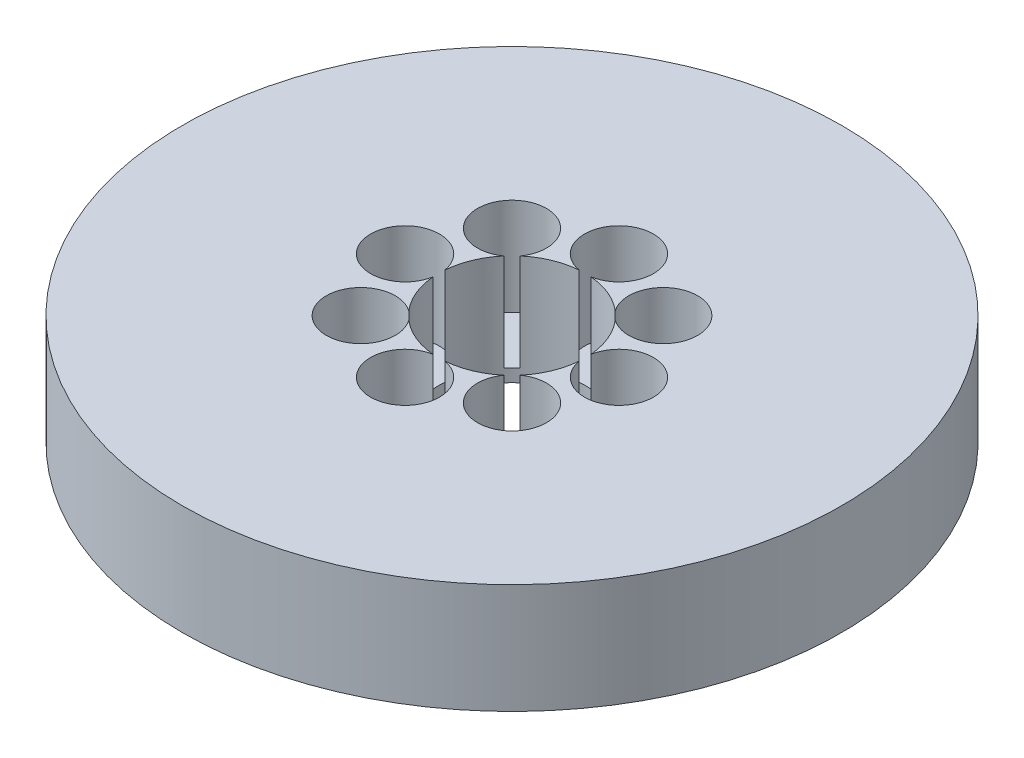
SolidWorks part; units mm, degrees
ref_plane "Front Plane" through (0, 0, 0) normal (0, 0, 1) x (1, 0, 0)
ref_plane "Top Plane" through (0, 0, 0) normal (0, 1, 0) x (1, 0, 0)
ref_plane "Right Plane" through (0, 0, 0) normal (1, 0, 0) x (0, 0, -1)
sketch "Sketch1" plane through (0, 0, 0) normal (0, 1, 0) x (1, 0, 0)
  circle A0 centre (0, 0) radius 90
  dimension "FLANGE_OD" = 180
extrude "Boss-Extrude1" add sketch "Sketch1" along normal blind 30
sketch "Sketch2" plane through (0, 0, 0) normal (0, 1, 0) x (1, 0, 0)
  circle A0 centre (0, 0) radius 20
  dimension "BORE_D" = 40
extrude "Cut-Extrude1" cut sketch "Sketch2" along normal through all
sketch "Sketch3" plane through (0, 30, 0) normal (0, 1, 0) x (1, 0, 0)
  circle A0 centre (0, 0) radius 29.2051 construction
  circle A1 centre (-29.2051, 0) radius 9.4037
  dimension "BOLT_D" = 18.8075
  dimension "BOLT_PCD" = 58.4101
extrude "Cut-Extrude2" cut sketch "Sketch3" against normal blind 26.5271
pattern_circular "CirPattern1" count 8 over 360 about axis through (0, 0, 0) along (0, 1, 0) of "Cut-Extrude2"
